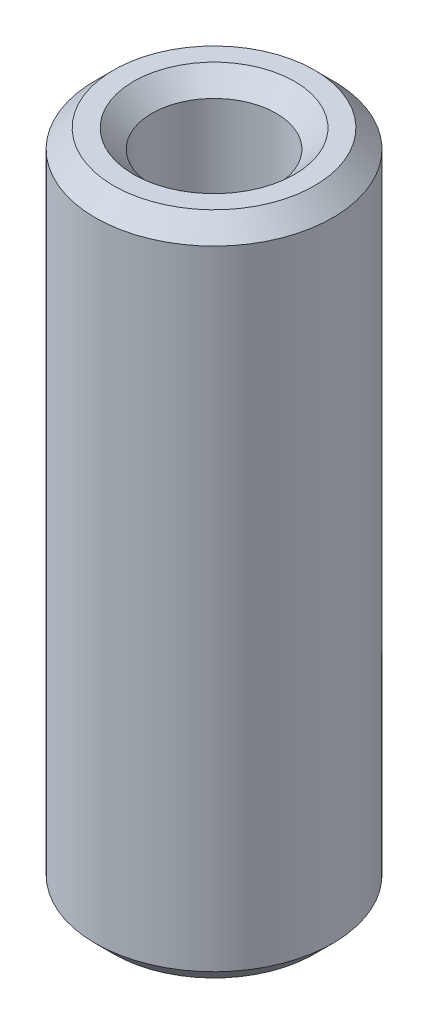
SolidWorks part; units mm, degrees
ref_plane "Front Plane" through (0, 0, 0) normal (0, 0, 1) x (1, 0, 0)
ref_plane "Top Plane" through (0, 0, 0) normal (0, 1, 0) x (1, 0, 0)
ref_plane "Right Plane" through (0, 0, 0) normal (1, 0, 0) x (0, 0, -1)
sketch "Sketch1" plane through (0, 0, 0) normal (0, 1, 0) x (1, 0, 0)
  circle A0 centre (0, 0) radius 10
  dimension "SLEEVE_OD" = 20
extrude "Boss-Extrude1" add sketch "Sketch1" along normal blind 56.0164
sketch "Sketch2" plane through (0, 0, 0) normal (0, 1, 0) x (1, 0, 0)
  circle A0 centre (0, 0) radius 5.2333
  dimension "BORE_D" = 10.4667
extrude "Cut-Extrude1" cut sketch "Sketch2" along normal through all
chamfer "Chamfer1" distance 1.5511 angle 45 4 edges at (0, 56.0164, 5.2333) (0, 0, 5.2333) (0, 0, 10) (0, 56.0164, 10)
